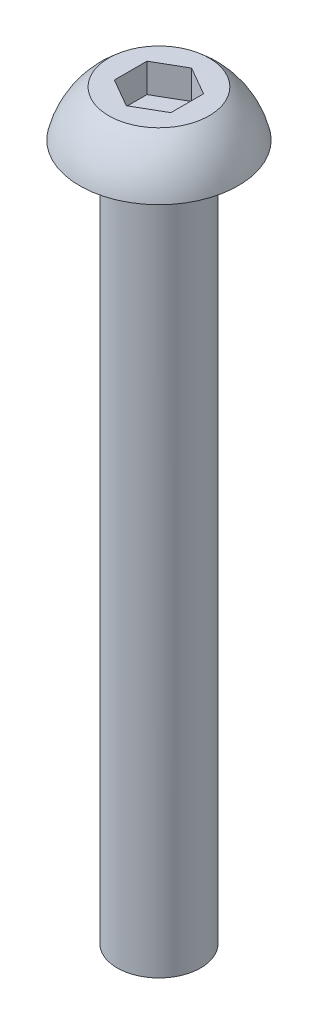
SolidWorks part; units mm, degrees
material "Plain Carbon Steel"
ref_plane "前视基准面" through (0, 0, 0) normal (0, 0, 1) x (1, 0, 0)
ref_plane "上视基准面" through (0, 0, 0) normal (0, 1, 0) x (1, 0, 0)
ref_plane "右视基准面" through (0, 0, 0) normal (1, 0, 0) x (0, 0, -1)
sketch "草图1" plane through (0, 0, 0) normal (0, 0, 1) x (1, 0, 0)
  line L0 (0, 2.3045) -> (-1.8, 2.3045)
  line L1 (0, 2.3045) -> (0, -24.3455)
  line L2 (-2.85, 0.6545) -> (-1.5, 0.6545)
  line L3 (0, -24.3455) -> (-1.5, -24.3455)
  line L4 (-1.5, -24.3455) -> (-1.5, 0.6545)
  line L5 (0, 0) -> (0, 50000) construction
  arc A0 (-1.8, 2.3045) -> (-2.85, 0.6545) centre (0, 0) ccw
  dimension "da" = 3.6
  dimension "dk" = 5.7
  dimension "d" = 3
  dimension "k" = 1.65
  dimension "L" = 25
revolve "旋转1" add sketch "草图1" angle 360 about L5
sketch "草图2" plane through (0, 2.3045, 0) normal (0, 1, 0) x (1, 0, 0)
  line L1 (0, -1.172) -> (1.015, -0.586)
  line L2 (1.015, -0.586) -> (1.015, 0.586)
  line L3 (1.015, 0.586) -> (0, 1.172)
  line L4 (0, 1.172) -> (-1.015, 0.586)
  line L5 (-1.015, 0.586) -> (-1.015, -0.586)
  line L6 (-1.015, -0.586) -> (0, -1.172)
  circle A0 centre (0, 0) radius 1.015 construction
  dimension "S" = 2.03
extrude "切除-拉伸1" cut sketch "草图2" against normal blind 1.04
fillet "圆角1" radius 0.1 1 edges at (0, 0.6545, -1.5)
